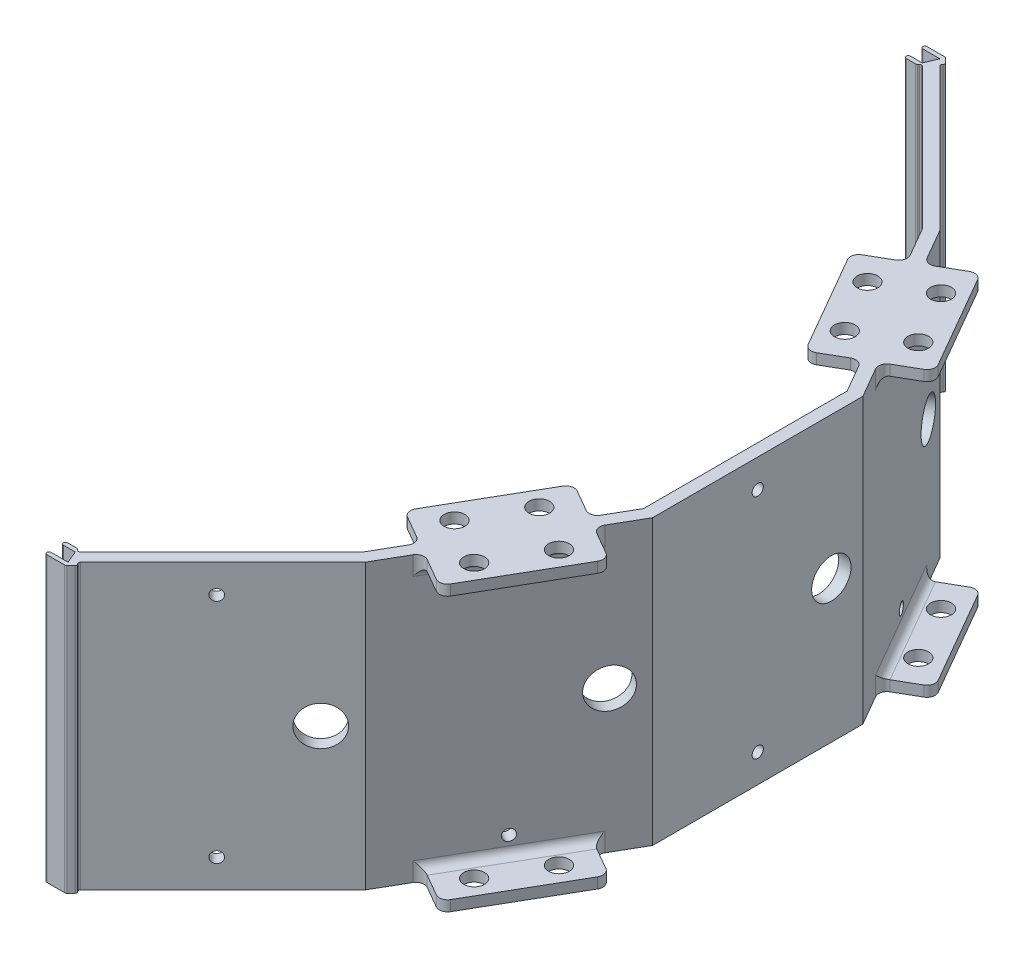
SolidWorks part; units mm, degrees
material "ABS"
ref_plane "Front Plane" through (0, 0, 0) normal (0, 0, 1) x (1, 0, 0)
ref_plane "Top Plane" through (0, 0, 0) normal (0, 1, 0) x (1, 0, 0)
ref_plane "Right Plane" through (0, 0, 0) normal (1, 0, 0) x (0, 0, -1)
sketch "Sketch1" plane through (0, 0, 0) normal (0, 1, 0) x (1, 0, 0)
  line L0 (-303.5027, 0) -> (303.5027, 0) construction
  line L1 (-223.52, -111.125) -> (223.52, -111.125)
  line L2 (-228.6, -106.045) -> (-228.6, 106.045)
  line L3 (-223.52, 111.125) -> (223.52, 111.125)
  line L4 (228.6, -106.045) -> (228.6, 106.045)
  line L5 (-228.6, -111.125) -> (228.6, 111.125) construction
  line L6 (-228.6, 111.125) -> (228.6, -111.125) construction
  line L7 (-303.5027, 36.5125) -> (303.5027, 36.5125) construction
  line L8 (-303.5027, -36.5125) -> (303.5027, -36.5125) construction
  line L9 (127, 111.125) -> (127, -111.125) construction
  line L10 (-142.24, 111.125) -> (-142.24, -111.125) construction
  arc A0 (223.52, 111.125) -> (228.6, 106.045) centre (223.52, 106.045) cw
  arc A1 (223.52, -111.125) -> (228.6, -106.045) centre (223.52, -106.045) ccw
  arc A2 (-223.52, -111.125) -> (-228.6, -106.045) centre (-223.52, -106.045) cw
  arc A3 (-228.6, 106.045) -> (-223.52, 111.125) centre (-223.52, 106.045) cw
  circle A4 centre (127, 36.5125) radius 2.54
  circle A5 centre (127, -36.5125) radius 2.54
  circle A6 centre (-142.24, 36.5125) radius 2.54
  circle A7 centre (-142.24, -36.5125) radius 2.54
  circle A8 centre (209.55, 0) radius 6.35
  point P0 (0, 0)
  point P20 (0, 0)
  point P37 (228.6, 0)
  dimension "D3" = 5.08
  dimension "D7" = 5.08
  dimension "D9" = 12.7
  dimension "D1" = 222.25
  dimension "D2" = 457.2
  dimension "D6" = 269.24
  dimension "D8" = 101.6
  dimension "D10" = 19.05
  dimension "D4" = 36.5125
  dimension "D5" = 36.5125
extrude "mainbaseplate" add sketch "Sketch1" along normal blind 3
sketch "Sketch2" plane through (0, 0, 0) normal (0, -1, 0) x (1, 0, 0)
  circle A0 centre (-142.24, 36.5125) radius 2.54 construction
  circle A1 centre (-142.24, -36.5125) radius 2.54 construction
  circle A2 centre (127, -36.5125) radius 2.54 construction
  circle A3 centre (127, 36.5125) radius 2.54 construction
  circle A4 centre (-142.24, 36.5125) radius 2.54
  circle A5 centre (-142.24, -36.5125) radius 2.54
  circle A6 centre (127, -36.5125) radius 2.54
  circle A7 centre (127, 36.5125) radius 2.54
  circle A8 centre (127, 36.5125) radius 6.096
  circle A9 centre (127, -36.5125) radius 6.096
  circle A10 centre (-142.24, -36.5125) radius 6.096
  circle A11 centre (-142.24, 36.5125) radius 6.096
  dimension "D1" = 12.192
extrude "BaseBoss-Extrude2" add sketch "Sketch2" along normal blind 10.16
sketch "Sketch3" plane through (0, 0, 0) normal (0, -1, 0) x (1, 0, 0)
  line L0 (-228.6, 0) -> (228.6, 0) construction
  line L1 (-228.6, -106.045) -> (-228.6, 106.045) construction
  line L2 (228.6, 106.045) -> (228.6, -106.045) construction
  line L3 (-228.6, 28.4) -> (-73.2, 28.4)
  line L4 (-228.6, -25.4) -> (-76.2, -25.4)
  line L6 (-228.6, 25.4) -> (-76.2, 25.4)
  line L7 (-76.2, -25.4) -> (-76.2, 25.4)
  line L8 (-228.6, -25.4) -> (-76.2, 25.4) construction
  line L9 (-228.6, 25.4) -> (-76.2, -25.4) construction
  line L10 (-73.2, -28.4) -> (-73.2, 28.4)
  line L11 (-228.6, -28.4) -> (-73.2, -28.4)
  line L12 (-228.6, 28.4) -> (-228.6, 25.4)
  line L13 (-228.6, -25.4) -> (-228.6, -28.4)
  point P6 (-152.4, 0)
  dimension "D1" = 50.8
  dimension "D2" = 152.4
  dimension "D3" = 76.2
  dimension "D4" = 3
extrude "Drive BatteryBoss-Extrude1" [suppressed] add sketch "Sketch3" along normal blind 28.575
sketch "Sketch4" [suppressed] plane through (0, -28.575, 0) normal (0, -1, 0) x (1, 0, 0)
  line L1 (-228.6, 28.4) -> (-73.2, 28.4)
  line L2 (-228.6, 28.4) -> (-228.6, -28.4)
  line L3 (-228.6, -28.4) -> (-73.2, -28.4)
  line L4 (-73.2, 28.4) -> (-73.2, -28.4)
extrude "drive Battery CapBoss-Extrude2" [suppressed] add sketch "Sketch4" along normal blind 3
sketch "Sketch5" [suppressed] plane through (0, -31.575, 0) normal (0, -1, 0) x (1, 0, 0)
  line L0 (-98.6, -28.4) -> (-73.2, -3)
  line L1 (-228.6, -28.4) -> (-73.2, -28.4) construction
  line L2 (-73.2, -28.4) -> (-73.2, 28.4) construction
  line L3 (-73.2, -3) -> (-52.1474, -3)
  line L4 (-52.1474, -3) -> (-52.1474, -43.6373)
  line L5 (-52.1474, -43.6373) -> (-98.6, -43.6373)
  line L6 (-98.6, -43.6373) -> (-98.6, -28.4)
  dimension "D1" = 25.4
  dimension "D2" = 25.4
  dimension "D3" = 21.0526
  dimension "D4" = 15.2373
extrude "Drive batterycutoutCut-Extrude1" [suppressed] cut sketch "Sketch5" against normal up to surface (31.575 mm away)
sketch "Sketch6" plane through (0, 3, 0) normal (0, 1, 0) x (1, 0, 0)
  line L0 (-228.6, 0) -> (228.6, 0) construction
  line L1 (-228.6, 106.045) -> (-228.6, -106.045) construction
  line L2 (228.6, -106.045) -> (228.6, 106.045) construction
  line L3 (-63.5, -41.1) -> (66.5, -41.1)
  line L4 (-63.5, -38.1) -> (63.5, -38.1)
  line L6 (-63.5, 38.1) -> (63.5, 38.1)
  line L7 (63.5, -38.1) -> (63.5, 38.1)
  line L8 (-63.5, -38.1) -> (63.5, 38.1) construction
  line L9 (-63.5, 38.1) -> (63.5, -38.1) construction
  line L10 (66.5, -41.1) -> (66.5, 41.1)
  line L11 (-63.5, 41.1) -> (66.5, 41.1)
  line L12 (-63.5, -41.1) -> (-63.5, -38.1)
  line L13 (-63.5, 38.1) -> (-63.5, 41.1)
  point P6 (0, 0)
  dimension "D1" = 127
  dimension "D2" = 76.2
  dimension "D4" = 63.5
  dimension "D3" = 3
extrude "PiBatteryBoxBoss-Extrude3" [suppressed] add sketch "Sketch6" along normal blind 25.4
sketch "Sketch7" [suppressed] plane through (0, 28.4, 0) normal (0, 1, 0) x (1, 0, 0)
  line L1 (66.5, 41.1) -> (-63.5, 41.1)
  line L2 (66.5, 41.1) -> (66.5, -41.1)
  line L3 (66.5, -41.1) -> (-63.5, -41.1)
  line L4 (-63.5, 41.1) -> (-63.5, -41.1)
extrude "PibatterytopBoss-Extrude4" [suppressed] add sketch "Sketch7" along normal blind 3
sketch "Sketch8" [suppressed] plane through (66.5, 0, 0) normal (1, 0, 0) x (0, 0, -1)
  line L0 (-38.1, 28.4) -> (38.1, 3) construction
  line L1 (38.1, 28.4) -> (-38.1, 28.4) construction
  line L2 (-31.75, 3) -> (31.75, 3)
  line L3 (-31.75, 3) -> (-31.75, 28.4)
  line L4 (-31.75, 28.4) -> (31.75, 28.4)
  line L5 (31.75, 3) -> (31.75, 28.4)
  line L6 (-31.75, 3) -> (31.75, 28.4) construction
  line L7 (-31.75, 28.4) -> (31.75, 3) construction
  point P2 (0, 15.7)
  dimension "D1" = 31.75
extrude "pibatterywiresCut-Extrude2" [suppressed] cut sketch "Sketch8" against normal blind 13.16
sketch "Sketch9" [suppressed] plane through (0, 31.4, 0) normal (0, 1, 0) x (1, 0, 0)
  line L0 (-63.5, 41.1) -> (66.5, -41.1) construction
  line L1 (-63.5, 0) -> (66.5, 0) construction
  line L2 (-5.08, -24.489) -> (52.92, -24.489) construction
  line L3 (-5.08, -24.489) -> (-5.08, 24.511) construction
  line L4 (-5.08, 24.511) -> (52.92, 24.511) construction
  line L5 (52.92, -24.489) -> (52.92, 24.511) construction
  line L6 (-5.08, -24.489) -> (52.92, 24.511) construction
  line L7 (-5.08, 24.511) -> (52.92, -24.489) construction
  line L8 (49.11, 20.701) -> (56.73, 20.701)
  line L9 (49.11, 20.701) -> (49.11, 28.321)
  line L10 (49.11, 28.321) -> (56.73, 28.321)
  line L11 (56.73, 20.701) -> (56.73, 28.321)
  line L12 (49.11, 20.701) -> (56.73, 28.321) construction
  line L13 (49.11, 28.321) -> (56.73, 20.701) construction
  line L14 (49.11, -28.299) -> (56.73, -28.299)
  line L16 (49.11, -20.679) -> (56.73, -20.679)
  line L18 (49.11, -28.299) -> (56.73, -20.679) construction
  line L19 (49.11, -20.679) -> (56.73, -28.299) construction
  line L20 (-8.89, 20.701) -> (-1.27, 20.701)
  line L21 (-8.89, 20.701) -> (-8.89, 28.321)
  line L22 (-8.89, 28.321) -> (-1.27, 28.321)
  line L23 (-1.27, 20.701) -> (-1.27, 28.321)
  line L24 (-8.89, 20.701) -> (-1.27, 28.321) construction
  line L25 (-8.89, 28.321) -> (-1.27, 20.701) construction
  line L26 (-8.89, -27.7078) -> (-1.27, -27.7078)
  line L27 (-8.89, -27.7078) -> (-8.89, -21.2702)
  line L28 (-8.89, -21.2702) -> (-1.27, -21.2702)
  line L29 (-1.27, -27.7078) -> (-1.27, -21.2702)
  line L30 (-8.89, -27.7078) -> (-1.27, -21.2702) construction
  line L31 (-8.89, -21.2702) -> (-1.27, -27.7078) construction
  line L32 (-63.5, 41.1) -> (-63.5, -41.1) construction
  line L33 (66.5, -41.1) -> (66.5, 41.1) construction
  line L34 (56.73, -20.679) -> (56.73, -28.299)
  line L35 (49.11, -20.679) -> (49.11, -28.299)
  circle A0 centre (52.92, 24.511) radius 1.35
  circle A1 centre (-5.08, 24.511) radius 1.35
  circle A2 centre (-5.08, -24.489) radius 1.35
  circle A3 centre (52.92, -24.489) radius 1.35
  point P4 (-8.057, 0)
  dimension "D3" = 2.7
  dimension "D4" = 7.62
  dimension "D1" = 58
  dimension "D2" = 49
  dimension "D5" = 7.62
  dimension "D6" = 7.62
  dimension "D7" = 7.62
  dimension "D8" = 7.62
  dimension "D9" = 7.62
  dimension "D10" = 58.42
  dimension "D11" = 24.511
  dimension "D12" = 7.62
extrude "PiBoardBoss-Extrude5" [suppressed] add sketch "Sketch9" along normal blind 3
sketch "Sketch10" plane through (0, 3, 0) normal (0, 1, 0) x (1, 0, 0)
  line L0 (228.6, 0) -> (-228.6, 0) construction
  line L1 (228.6, -106.045) -> (228.6, 106.045) construction
  line L2 (-228.6, 106.045) -> (-228.6, -106.045) construction
  line L3 (104.95, 18.875) -> (174.45, 18.875)
  line L4 (107.95, -15.875) -> (171.45, -15.875)
  line L5 (107.95, -15.875) -> (107.95, -6.175)
  line L6 (107.95, 15.875) -> (171.45, 15.875)
  line L7 (171.45, -15.875) -> (171.45, 15.875)
  line L8 (107.95, -15.875) -> (171.45, 15.875) construction
  line L9 (107.95, 15.875) -> (171.45, -15.875) construction
  line L10 (174.45, -18.875) -> (174.45, 18.875)
  line L11 (104.95, -18.875) -> (174.45, -18.875)
  line L12 (104.95, -18.875) -> (104.95, -6.175)
  line L13 (104.95, 6.175) -> (107.95, 6.175)
  line L14 (104.95, -6.175) -> (107.95, -6.175)
  line L15 (104.95, 6.175) -> (104.95, 18.875)
  line L16 (104.95, -18.875) -> (104.95, 18.875) construction
  line L17 (107.95, 6.175) -> (107.95, 15.875)
  line L18 (107.95, -15.875) -> (107.95, 15.875) construction
  point P6 (139.7, 0)
  dimension "D1" = 31.75
  dimension "D2" = 63.5
  dimension "D3" = 139.7
  dimension "D5" = 12.7
  dimension "D6" = 12.7
  dimension "D4" = 3
extrude "PanTilt-Extrude6" [suppressed] add sketch "Sketch10" along normal blind 53.34
sketch "Sketch11" [suppressed] plane through (0, 56.34, 0) normal (0, 1, 0) x (1, 0, 0)
  line L1 (104.95, 18.875) -> (174.45, 18.875)
  line L2 (104.95, 18.875) -> (104.95, -18.875)
  line L3 (104.95, -18.875) -> (174.45, -18.875)
  line L4 (174.45, 18.875) -> (174.45, -18.875)
extrude "Boss-Extrude7" [suppressed] add sketch "Sketch11" along normal blind 3
sketch "Sketch12" [suppressed] plane through (0, 59.34, 0) normal (0, 1, 0) x (1, 0, 0)
  line L0 (104.95, 0) -> (174.45, 0) construction
  line L1 (104.95, 18.875) -> (104.95, -18.875) construction
  line L2 (174.45, -18.875) -> (174.45, 18.875) construction
  line L3 (118.745, 1.9377) -> (104.95, 1.9377)
  line L4 (118.745, -10.795) -> (160.655, -10.795)
  line L5 (118.745, -10.795) -> (118.745, -1.9901)
  line L6 (118.745, 10.795) -> (160.655, 10.795)
  line L7 (160.655, -10.795) -> (160.655, 10.795)
  line L8 (118.745, -10.795) -> (160.655, 10.795) construction
  line L9 (118.745, 10.795) -> (160.655, -10.795) construction
  line L10 (115.57, -5.08) -> (163.83, -5.08) construction
  line L11 (115.57, -5.08) -> (115.57, 5.08) construction
  line L12 (115.57, 5.08) -> (163.83, 5.08) construction
  line L13 (163.83, -5.08) -> (163.83, 5.08) construction
  line L14 (115.57, -5.08) -> (163.83, 5.08) construction
  line L15 (115.57, 5.08) -> (163.83, -5.08) construction
  line L16 (118.745, -1.9901) -> (104.95, -1.9901)
  line L17 (118.745, 1.9377) -> (118.745, 10.795)
  line L18 (104.95, 1.9377) -> (95.8416, 0)
  line L19 (95.8416, 0) -> (104.95, -1.9901)
  circle A0 centre (163.83, 5.08) radius 2.0193
  circle A1 centre (163.83, -5.08) radius 2.0193
  circle A2 centre (115.57, 5.08) radius 2.0193
  circle A3 centre (115.57, -5.08) radius 2.0193
  point P6 (139.7, 0)
  point P11 (139.7, 0)
  dimension "D5" = 4.0386
  dimension "D1" = 21.59
  dimension "D2" = 41.91
  dimension "D3" = 48.26
  dimension "D4" = 10.16
  dimension "D6" = 1.9377
  dimension "D7" = 1.9901
extrude "Cut-Extrude3" [suppressed] cut sketch "Sketch12" against normal up to surface (56.34 mm away)
sketch "Sketch13" plane through (0, 3, 0) normal (0, 1, 0) x (1, 0, 0)
  line L0 (228.6, 0) -> (-228.6, 0) construction
  line L1 (228.6, -106.045) -> (228.6, 106.045) construction
  line L2 (-228.6, 106.045) -> (-228.6, -106.045) construction
  line L3 (198.12, 0) -> (198.12, 25.4)
  line L4 (198.12, 25.4) -> (172.72, 69.3941)
  line L5 (172.72, 69.3941) -> (136.799, 105.3151)
  line L6 (198.12, 25.4) -> (198.12, 129.9736) construction
  line L7 (172.72, 69.3941) -> (172.72, 97.5573) construction
  line L8 (136.799, 105.3151) -> (-185.781, 105.3151)
  line L9 (-185.781, 105.3151) -> (-221.702, 69.3941)
  line L10 (-221.702, 69.3941) -> (-221.702, 0)
  line L11 (-185.781, 105.3151) -> (-290.6809, 105.3151) construction
  line L12 (195.12, 0) -> (195.12, 24.5962)
  line L13 (195.12, 24.5962) -> (170.3194, 67.552)
  line L14 (170.3194, 67.552) -> (135.5563, 102.3151)
  line L15 (135.5563, 102.3151) -> (-184.5384, 102.3151)
  line L16 (-184.5384, 102.3151) -> (-218.702, 68.1514)
  line L17 (-218.702, 68.1514) -> (-218.702, 0)
  line L18 (172.72, -69.3941) -> (172.72, -97.5573) construction
  line L19 (198.12, -25.4) -> (198.12, -129.9736) construction
  line L20 (-218.702, -68.1514) -> (-218.702, 0)
  line L21 (-184.5384, -102.3151) -> (-218.702, -68.1514)
  line L22 (135.5563, -102.3151) -> (-184.5384, -102.3151)
  line L23 (170.3194, -67.552) -> (135.5563, -102.3151)
  line L24 (195.12, -24.5962) -> (170.3194, -67.552)
  line L25 (195.12, 0) -> (195.12, -24.5962)
  line L26 (-221.702, -69.3941) -> (-221.702, 0)
  line L27 (-185.781, -105.3151) -> (-221.702, -69.3941)
  line L28 (136.799, -105.3151) -> (-185.781, -105.3151)
  line L29 (172.72, -69.3941) -> (136.799, -105.3151)
  line L30 (198.12, -25.4) -> (172.72, -69.3941)
  line L31 (198.12, 0) -> (198.12, -25.4)
  line L32 (136.799, -105.3151) -> (135.5563, -102.3151)
  line L33 (135.5563, 102.3151) -> (136.799, 105.3151)
  line L34 (137.9705, 104.1435) -> (138.6777, 104.8506)
  line L35 (138.6777, 104.8506) -> (137.2132, 106.3151)
  line L36 (137.2132, 106.3151) -> (132.1937, 106.3151)
  line L37 (132.1937, 106.3151) -> (132.1937, 105.3151)
  line L38 (132.1937, 106.3151) -> (132.1937, -67.049) construction
  line L39 (135.8492, 102.0222) -> (135.1421, 101.3151)
  line L40 (135.1421, 101.3151) -> (135.1421, 101.3151)
  line L41 (135.1421, 101.3151) -> (132.1937, 101.3151)
  line L42 (132.1937, 101.3151) -> (132.1937, 102.3151)
  line L43 (132.1937, -67.049) -> (132.1937, -124.425) construction
  line L44 (135.8492, -102.0222) -> (135.1421, -101.3151)
  line L45 (135.1421, -101.3151) -> (135.1421, -101.3151)
  line L46 (135.1421, -101.3151) -> (132.1937, -101.3151)
  line L47 (132.1937, -101.3151) -> (132.1937, -102.3151)
  line L48 (132.1937, -106.3151) -> (132.1937, -105.3151)
  line L49 (137.2132, -106.3151) -> (132.1937, -106.3151)
  line L50 (138.6777, -104.8506) -> (137.2132, -106.3151)
  line L51 (137.9705, -104.1435) -> (138.6777, -104.8506)
  point P58 (0, 0)
  point P59 (0, 0)
  point P60 (0, 0)
  point P61 (0, 0)
  dimension "D1" = 30.48
  dimension "D2" = 25.4
  dimension "D3" = 30
  dimension "D4" = 50.8
  dimension "D5" = 45
  dimension "D6" = 50.8
  dimension "D7" = 322.58
  dimension "D8" = 50.8
  dimension "D9" = 45
  dimension "D11" = 1
  dimension "D12" = 1
  dimension "D13" = 1
  dimension "D15" = 1
  dimension "D10" = 3
extrude "Bottom Shell WallsBoss-Extrude8" add sketch "Sketch13" along normal blind 68.58 contours L33 L14 L13 L12 L25 L24 L23 L32 L29 L30 L31 L3 L4 L5 | L51 L29 L28 L48 L49 L50 | L46 L47 L22 L23 L44 L45 | L36 L37 L8 L5 L34 L35 | L42 L41 L40 L39 L14 L15 region at (195.9227, 3, 12.7) region at (135.4596, 3, -105.6407) region at (135.4596, 3, 105.6407) region at (133.881, 3, -101.8296) region at (133.881, 3, 101.8296)
sketch "Sketch14" plane through (121.057, 0, -121.057) normal (0.7071, 0, -0.7071) x (-0.7071, 0, -0.7071)
  line L0 (-47.6625, 71.58) -> (-47.6625, 3) construction
  line L1 (-73.0625, 71.58) -> (-22.2625, 71.58) construction
  line L2 (-73.0625, 3) -> (-23.9193, 3) construction
  line L3 (-47.6625, 37.29) -> (-25.0131, 37.29) construction
  circle A0 centre (-47.6625, 64.722) radius 1.3526
  circle A1 centre (-47.6625, 9.858) radius 1.3526
  circle A2 centre (-29.8825, 37.29) radius 4.7625
  point P10 (-47.6625, 37.29)
  dimension "D1" = 2.7051
  dimension "D4" = 9.525
  dimension "D2" = 54.864
  dimension "D3" = 27.432
  dimension "D5" = 17.78
extrude "Sharp1Cut-Extrude4" cut sketch "Sketch14" against normal blind 12.7
sketch "Sketch15" plane through (159.5885, 0, -92.1385) normal (0.866, 0, -0.5) x (-0.5, 0, -0.866)
  line L0 (-51.663, 71.58) -> (-51.663, 3) construction
  line L1 (-77.063, 71.58) -> (-26.263, 71.58) construction
  line L2 (-77.063, 3) -> (-26.263, 3) construction
  line L3 (-51.663, 37.29) -> (-29.7061, 37.29) construction
  circle A0 centre (-51.663, 64.722) radius 1.3526
  circle A1 centre (-51.663, 9.858) radius 1.3526
  circle A2 centre (-33.883, 37.29) radius 4.7625
  point P10 (-51.663, 37.29)
  dimension "D1" = 2.7051
  dimension "D4" = 9.525
  dimension "D2" = 27.432
  dimension "D3" = 54.864
  dimension "D5" = 17.78
extrude "Sharp2Cut-Extrude5" cut sketch "Sketch15" against normal blind 7.62
sketch "Sketch16" plane through (198.12, 0, 0) normal (1, 0, 0) x (0, 0, -1)
  line L0 (0, 71.58) -> (0, 3) construction
  line L1 (-25.4, 71.58) -> (25.4, 71.58) construction
  line L2 (-25.4, 3) -> (25.4, 3) construction
  line L3 (0, 37.29) -> (21.2381, 37.29) construction
  circle A0 centre (0, 64.722) radius 1.3526
  circle A1 centre (0, 9.858) radius 1.3525
  circle A2 centre (17.78, 37.29) radius 4.7625
  dimension "D1" = 2.7051
  dimension "D4" = 9.525
  dimension "D2" = 27.432
  dimension "D3" = 54.864
  dimension "D5" = 17.78
extrude "Sharp3Cut-Extrude6" cut sketch "Sketch16" against normal blind 7.62
sketch "Sketch17" plane through (159.5885, 0, 92.1385) normal (0.866, 0, 0.5) x (0.5, 0, -0.866)
  line L0 (51.663, 71.58) -> (51.663, 3) construction
  line L1 (26.263, 71.58) -> (77.063, 71.58) construction
  line L2 (26.263, 3) -> (77.063, 3) construction
  line L3 (51.663, 37.29) -> (70.4023, 37.29) construction
  circle A0 centre (51.663, 64.722) radius 1.3526
  circle A1 centre (51.663, 9.858) radius 1.3526
  circle A2 centre (69.443, 37.29) radius 4.7625
  dimension "D1" = 2.7051
  dimension "D2" = 2.7051
  dimension "D3" = 9.525
  dimension "D4" = 17.78
  dimension "D5" = 27.432
  dimension "D6" = 54.864
extrude "SharpCut-Extrude7" cut sketch "Sketch17" against normal blind 7.62
sketch "Sketch18" plane through (121.057, 0, 121.057) normal (0.7071, 0, 0.7071) x (0.7071, 0, -0.7071)
  line L0 (47.6625, 71.58) -> (47.6625, 3) construction
  line L1 (22.2625, 71.58) -> (73.0625, 71.58) construction
  line L2 (23.9193, 3) -> (73.0625, 3) construction
  line L3 (25.604, 37.29) -> (69.7209, 37.29) construction
  circle A0 centre (47.6625, 64.722) radius 1.3526
  circle A1 centre (47.6625, 9.858) radius 1.3526
  circle A2 centre (65.4425, 37.29) radius 4.7625
  point P13 (47.6625, 37.29)
  dimension "D1" = 9.525
  dimension "D3" = 2.7051
  dimension "D4" = 2.7051
  dimension "D2" = 17.78
  dimension "D5" = 27.432
  dimension "D6" = 54.864
extrude "SharpCut-Extrude8" cut sketch "Sketch18" against normal blind 7.62
sketch "Sketch19" [suppressed] plane through (0, 71.58, 0) normal (0, 1, 0) x (1, 0, 0)
  line L0 (-223.52, -111.125) -> (223.52, -111.125) construction
  line L1 (228.6, -106.045) -> (228.6, 106.045) construction
  line L2 (223.52, 111.125) -> (-223.52, 111.125) construction
  line L3 (104.95, -111.125) -> (223.52, -111.125)
  line L4 (228.6, -106.045) -> (228.6, 106.045)
  line L5 (223.52, 111.125) -> (104.95, 111.125)
  line L6 (104.95, 111.125) -> (104.95, -111.125)
  arc A0 (223.52, -111.125) -> (228.6, -106.045) centre (223.52, -106.045) ccw construction
  arc A1 (228.6, 106.045) -> (223.52, 111.125) centre (223.52, 106.045) ccw construction
  arc A2 (223.52, -111.125) -> (228.6, -106.045) centre (223.52, -106.045) ccw
  arc A3 (228.6, 106.045) -> (223.52, 111.125) centre (223.52, 106.045) ccw
sketch "Sketch21" [suppressed] plane through (0, 74.58, 0) normal (0, 1, 0) x (1, 0, 0)
  line L0 (104.95, -18.875) -> (174.45, -18.875) construction
  line L1 (174.45, -18.875) -> (174.45, 18.875) construction
  line L2 (174.45, 18.875) -> (104.95, 18.875) construction
  line L3 (104.95, -18.875) -> (164.29, -18.875)
  line L4 (174.45, -8.715) -> (174.45, 8.715)
  line L5 (164.29, 18.875) -> (104.95, 18.875)
  line L6 (104.95, 18.875) -> (84.8462, 2.2825)
  line L7 (84.8462, 2.2825) -> (104.95, -18.875)
  arc A0 (164.29, -18.875) -> (174.45, -8.715) centre (164.29, -8.715) ccw
  arc A1 (174.45, 8.715) -> (164.29, 18.875) centre (164.29, 8.715) ccw
  circle A2 centre (127, -36.5125) radius 6.096 construction
  circle A3 centre (127, 36.5125) radius 6.096 construction
  circle A4 centre (127, -36.5125) radius 6.096
  circle A5 centre (127, 36.5125) radius 6.096
  dimension "D1" = 10.16
extrude "topsensorplateCut-Extrude4" [suppressed] cut sketch "Sketch21" against normal blind 8.08
sketch "Sketch22" [suppressed] plane through (0, 0, 0) normal (0, -1, 0) x (1, 0, 0)
  line L0 (228.6, 0) -> (-228.6, 0) construction
  line L1 (228.6, 106.045) -> (228.6, -106.045) construction
  line L2 (-228.6, 28.4) -> (-228.6, -28.4) construction
  line L3 (220.98, 0) -> (220.98, 76.2)
  line L4 (220.98, 76.2) -> (193.675, 103.505)
  line L5 (193.675, 103.505) -> (-25.4, 103.505)
  line L6 (-223.52, 111.125) -> (223.52, 111.125) construction
  line L7 (217.98, 0) -> (217.98, 74.9574)
  line L8 (217.98, 74.9574) -> (192.4324, 100.505)
  line L9 (192.4324, 100.505) -> (-25.4, 100.505)
  line L10 (-25.4, 103.505) -> (-25.4, 100.505)
  line L11 (217.98, 0) -> (217.98, -74.9574)
  line L12 (220.98, 0) -> (220.98, -76.2)
  line L13 (-25.4, -103.505) -> (-25.4, -100.505)
  line L14 (192.4324, -100.505) -> (-25.4, -100.505)
  line L15 (217.98, -74.9574) -> (192.4324, -100.505)
  line L16 (193.675, -103.505) -> (-25.4, -103.505)
  line L17 (220.98, -76.2) -> (193.675, -103.505)
  line L18 (-220.98, 28.4) -> (-220.98, 76.2)
  line L19 (-73.2, 28.4) -> (-228.6, 28.4) construction
  line L20 (-220.98, 76.2) -> (-193.548, 103.505)
  line L21 (-193.548, 103.505) -> (-127, 103.505)
  line L22 (-228.6, 28.4) -> (-228.6, 106.045) construction
  line L23 (-217.98, 28.4) -> (-217.98, 74.9533)
  line L24 (-217.98, 74.9533) -> (-192.3094, 100.505)
  line L25 (-192.3094, 100.505) -> (-127, 100.505)
  line L26 (-127, 103.505) -> (-127, 100.505)
  line L27 (-220.98, 28.4) -> (-217.98, 28.4)
  line L28 (-127, -103.505) -> (-127, -100.505)
  line L29 (-192.3094, -100.505) -> (-127, -100.505)
  line L30 (-217.98, -74.9533) -> (-192.3094, -100.505)
  line L31 (-217.98, -28.4) -> (-217.98, -74.9533)
  line L32 (-193.548, -103.505) -> (-127, -103.505)
  line L33 (-220.98, -76.2) -> (-193.548, -103.505)
  line L34 (-220.98, -28.4) -> (-220.98, -76.2)
  line L35 (-220.98, -28.4) -> (-217.98, -28.4)
  dimension "D1" = 7.62
  dimension "D2" = 7.62
  dimension "D3" = 76.2
  dimension "D4" = 34.925
  dimension "D5" = 254
  dimension "D7" = 7.62
  dimension "D8" = 76.2
  dimension "D9" = 7.62
  dimension "D10" = 101.6
  dimension "D11" = 35.052
  dimension "D6" = 3
  dimension "D12" = 3
sketch "Sketch23" [suppressed] plane through (0, 0, -103.505) normal (0, 0, -1) x (-1, 0, 0)
  line L0 (25.4, 0) -> (-193.675, 0) construction
  line L2 (-223.1134, -81.0052) -> (22.7571, -81.0052) construction
  line L3 (22.7571, -81.0052) -> (254.0819, -81.0052) construction
  circle A1 centre (-127, -81.0052) radius 63.5
  circle A2 centre (152.4, -81.0052) radius 63.5
  dimension "D1" = 81.0052
  dimension "D4" = 127
  dimension "D2" = 22.7571
  dimension "D3" = 223.1134
  dimension "D5" = 127
  dimension "D6" = 279.4
extrude "TireCut-Extrude5" [suppressed] cut sketch "Sketch23" against normal blind 25.4
sketch "Sketch28" [suppressed] plane through (0, 0, 103.505) normal (0, 0, 1) x (1, 0, 0)
  line L0 (-205.194, -45.72) -> (-93.1399, -108.4782)
  line L1 (-93.1399, -108.4782) -> (179.794, -45.72)
  line L2 (74.206, -45.72) -> (-102.0458, -69.7467)
  line L3 (-102.0458, -69.7467) -> (-127, -22.8065)
  arc A0 (-192.3094, -31.6141) -> (-205.194, -45.72) centre (-152.4, -81.0052) ccw construction
  arc A1 (-127, -22.8065) -> (-192.3094, -31.6141) centre (-152.4, -81.0052) ccw construction
  arc A2 (179.794, -45.72) -> (74.206, -45.72) centre (127, -81.0052) ccw construction
  arc A3 (-192.3094, -31.6141) -> (-205.194, -45.72) centre (-152.4, -81.0052) ccw
  arc A4 (-127, -22.8065) -> (-192.3094, -31.6141) centre (-152.4, -81.0052) ccw
  arc A5 (179.794, -45.72) -> (74.206, -45.72) centre (127, -81.0052) ccw
extrude "TireCut-Extrude8" [suppressed] cut sketch "Sketch28" against normal blind 35.56
sketch "Sketch30" [suppressed] plane through (0, 74.58, 0) normal (0, 1, 0) x (1, 0, 0)
  line L0 (-147.32, 0) -> (-228.6, 0) construction
  line L1 (-147.32, -111.125) -> (-147.32, 111.125) construction
  line L2 (-228.6, 106.045) -> (-228.6, -106.045) construction
  circle A0 centre (-166.37, 0) radius 6.35
  dimension "D1" = 12.7
  dimension "D2" = 19.05
extrude "Cut-Extrude10" [suppressed] cut sketch "Sketch30" against normal blind 11.684
sketch "Sketch31" [suppressed] plane through (0, 0, 0) normal (1, 0, 0) x (0, 0, -1)
  line L0 (102.3151, 71.58) -> (102.3151, 3) construction
  line L1 (-102.3151, 71.58) -> (-76.9151, 71.58)
  line L2 (-102.3151, 71.58) -> (-102.3151, 68.58)
  line L3 (-102.3151, 68.58) -> (-76.9151, 68.58)
  line L4 (102.3151, 71.58) -> (102.3151, 68.58)
  line L5 (-76.9151, 71.58) -> (-76.9151, 68.58)
  line L6 (76.9151, 71.58) -> (76.9151, 68.58)
  line L7 (76.9151, 71.58) -> (102.3151, 71.58)
  line L8 (76.9151, 68.58) -> (102.3151, 68.58)
  dimension "D1" = 3
  dimension "D2" = 25.4
  dimension "D3" = 25.4
fillet "Fillet1" radius 0.5 18 edges at (138.6777, 37.29, 104.8506) (137.9705, 37.29, 104.1435) (138.6777, 37.29, -104.8506) (137.9705, 37.29, -104.1435) (132.1937, 37.29, 101.3151) (132.1937, 37.29, 102.3151) (135.1421, 37.29, 101.3151) (135.8492, 37.29, 102.0222) (132.1937, 37.29, 105.3151) (132.1937, 37.29, 106.3151) (137.2132, 37.29, 106.3151) (135.1421, 37.29, -101.3151) (135.8492, 37.29, -102.0222) (132.1937, 37.29, -102.3151) (132.1937, 37.29, -101.3151) (132.1937, 37.29, -106.3151) (132.1937, 37.29, -105.3151) (137.2132, 37.29, -106.3151)
sketch "Sketch32" plane through (0, -10.16, 0) normal (0, -1, 0) x (1, 0, 0)
  line L1 (254.5459, -134.1156) -> (-317.1071, -134.1156)
  line L2 (254.5459, -134.1156) -> (254.5459, 140.3717)
  line L3 (254.5459, 140.3717) -> (-317.1071, 140.3717)
  line L4 (-317.1071, -134.1156) -> (-317.1071, 140.3717)
extrude "Cut-Extrude11" cut sketch "Sketch32" against normal up to surface (13.16 mm away) up to face at (144.5082, 3, 0)
sketch "Sketch34" plane through (0, 3, 0) normal (0, -1, 0) x (1, 0, 0)
  line L0 (177.92, 60.3874) -> (186.5803, 65.3874)
  line L5 (198.12, 25.4) -> (172.72, 69.3941) construction
  line L6 (186.5803, 65.3874) -> (201.5803, 39.4067)
  line L7 (181.6617, 27.9067) -> (166.6617, 53.8874)
  line L8 (166.6617, 53.8874) -> (175.3219, 58.8874)
  line L9 (195.12, 24.5962) -> (170.3194, 67.552) construction
  line L10 (201.5803, 39.4067) -> (181.6617, 27.9067)
  line L11 (194.0803, 52.397) -> (174.1617, 40.897) construction
  line L12 (191.621, 33.6567) -> (183.9986, 46.8591) construction
  line L13 (182.2501, 62.8874) -> (189.7501, 49.897) construction
  line L14 (198.12, 0) -> (15.3913, 0) construction
  line L15 (198.12, -25.4) -> (198.12, 25.4) construction
  line L16 (201.5803, -39.4067) -> (181.6617, -27.9067)
  line L17 (186.5803, -65.3874) -> (201.5803, -39.4067)
  line L18 (177.92, -60.3874) -> (186.5803, -65.3874)
  line L19 (166.6617, -53.8874) -> (175.3219, -58.8874)
  line L20 (181.6617, -27.9067) -> (166.6617, -53.8874)
  circle A0 centre (186.0001, 56.3922) radius 2.5
  circle A1 centre (174.7418, 49.8922) radius 2.5
  circle A2 centre (193.5001, 43.4019) radius 2.5
  circle A3 centre (182.2418, 36.9019) radius 2.5
  circle A4 centre (174.7418, -49.8922) radius 2.5
  circle A5 centre (186.0001, -56.3922) radius 2.5
  circle A6 centre (193.5001, -43.4019) radius 2.5
  circle A7 centre (182.2418, -36.9019) radius 2.5
  point P16 (185.42, 47.397)
  point P18 (186.0001, 56.3922)
  line M6 (170.3194, 67.552) -> (195.12, 24.5962)
  line M8 (195.12, -24.5962) -> (170.3194, -67.552)
  line M27 (172.72, -69.3941) -> (198.12, -25.4)
  line M29 (198.12, 25.4) -> (172.72, 69.3941)
  dimension "D4" = 5
  dimension "D1" = 10
  dimension "D2" = 10
  dimension "D3" = 30
extrude "Boss-Extrude8" add sketch "Sketch34" against normal blind 2.54 contours L18 L17 L16 A6 A5 M27 | L16 L20 L19 A4 A7 M8 | L10 L8 L7 A3 A1 M6 | L10 L6 L0 A0 A2 M29 region at (178.4918, 3, 43.397) region at (189.7501, 3, 49.897) region at (189.7501, 3, -49.897) region at (178.4918, 3, -43.397)
sketch "Sketch36" plane through (0, 71.58, 0) normal (0, 1, 0) x (1, 0, 0)
  line L0 (177.92, -60.3874) -> (186.5803, -65.3874) construction
  line L1 (186.5803, -65.3874) -> (201.5803, -39.4067) construction
  line L2 (201.5803, -39.4067) -> (181.6617, -27.9067) construction
  line L3 (181.6617, -27.9067) -> (166.6617, -53.8874) construction
  line L4 (166.6617, -53.8874) -> (175.3219, -58.8874) construction
  line L5 (166.6617, 53.8874) -> (175.3219, 58.8874) construction
  line L6 (181.6617, 27.9067) -> (166.6617, 53.8874) construction
  line L7 (201.5803, 39.4067) -> (181.6617, 27.9067) construction
  line L8 (186.5803, 65.3874) -> (201.5803, 39.4067) construction
  line L9 (177.92, 60.3874) -> (186.5803, 65.3874) construction
  line L10 (177.92, -60.3874) -> (186.5803, -65.3874)
  line L11 (186.5803, -65.3874) -> (201.5803, -39.4067)
  line L16 (201.5803, -39.4067) -> (181.6617, -27.9067)
  line L17 (181.6617, -27.9067) -> (166.6617, -53.8874)
  line L18 (166.6617, -53.8874) -> (175.3219, -58.8874)
  line L19 (166.6617, 53.8874) -> (175.3219, 58.8874)
  line L20 (181.6617, 27.9067) -> (166.6617, 53.8874)
  line L21 (201.5803, 39.4067) -> (181.6617, 27.9067)
  line L22 (186.5803, 65.3874) -> (201.5803, 39.4067)
  line L23 (177.92, 60.3874) -> (186.5803, 65.3874)
  line L24 (175.3219, 58.8874) -> (177.92, 60.3874)
  line L25 (175.3219, -58.8874) -> (177.92, -60.3874)
  circle A1 centre (186.0001, -56.3922) radius 2.5
  circle A2 centre (186.0001, -56.3922) radius 2.5
  circle A3 centre (182.2418, -36.9019) radius 2.5
  circle A4 centre (182.2418, -36.9019) radius 2.5
  circle A5 centre (193.5001, -43.4019) radius 2.5
  circle A6 centre (193.5001, -43.4019) radius 2.5
  circle A7 centre (174.7418, -49.8922) radius 2.5
  circle A8 centre (174.7418, -49.8922) radius 2.5
  circle A9 centre (182.2418, 36.9019) radius 2.5
  circle A10 centre (182.2418, 36.9019) radius 2.5
  circle A11 centre (193.5001, 43.4019) radius 2.5
  circle A12 centre (193.5001, 43.4019) radius 2.5
  circle A13 centre (186.0001, 56.3922) radius 2.5
  circle A14 centre (186.0001, 56.3922) radius 2.5
  circle A15 centre (174.7418, 49.8922) radius 2.5
  circle A16 centre (174.7418, 49.8922) radius 2.5
  line M23 (172.72, -69.3941) -> (198.12, -25.4)
  line M25 (198.12, 25.4) -> (172.72, 69.3941)
  line M44 (170.3194, 67.552) -> (195.12, 24.5962)
  line M46 (195.12, -24.5962) -> (170.3194, -67.552)
  dimension "D1" = 0
  dimension "D2" = 0
  dimension "D3" = 0
  dimension "D4" = 0
  dimension "D5" = 0
  dimension "D6" = 0
  dimension "D7" = 0
  dimension "D8" = 0
extrude "Boss-Extrude9" add sketch "Sketch36" against normal blind 2.54 contours L23 L21 L22 A14 A12 M25 | L21 L19 L20 A16 A10 M44 | L17 L18 L16 A8 A4 M46 | L11 L16 L10 A6 A2 M23 | L25 L16 M46 M23 | L24 L21 M44 M25 region at (189.7501, 71.58, 49.897) region at (184.121, 71.58, 46.647) region at (178.4918, 71.58, 43.397) region at (178.4918, 71.58, -43.397) region at (184.121, 71.58, -46.647) region at (189.7501, 71.58, -49.897)
fillet "Fillet2" radius 2 20 edges at (166.6617, 4.27, 53.8874) (181.6617, 4.27, 27.9067) (190.3219, 4.27, 32.9067) (175.3219, 4.27, 58.8874) (182.8219, 5.54, 45.897) (166.6617, 4.27, -53.8874) (181.6617, 4.27, -27.9067) (190.3219, 4.27, -32.9067) (175.3219, 4.27, -58.8874) (182.8219, 5.54, -45.897) (201.5803, 4.27, 39.4067) (186.5803, 4.27, 65.3874) (177.92, 4.27, 60.3874) (192.92, 4.27, 34.4067) (185.42, 5.54, 47.397) (201.5803, 4.27, -39.4067) (186.5803, 4.27, -65.3874) (177.92, 4.27, -60.3874) (192.92, 4.27, -34.4067) (185.42, 5.54, -47.397)
fillet "Fillet3" radius 2 20 edges at (181.6617, 70.31, 27.9067) (190.3219, 70.31, 32.9067) (175.3219, 70.31, 58.8874) (166.6617, 70.31, 53.8874) (182.8219, 69.04, 45.897) (190.3219, 70.31, -32.9067) (181.6617, 70.31, -27.9067) (166.6617, 70.31, -53.8874) (182.8219, 69.04, -45.897) (175.3219, 70.31, -58.8874) (192.92, 70.31, 34.4067) (201.5803, 70.31, 39.4067) (177.92, 70.31, 60.3874) (185.42, 69.04, 47.397) (186.5803, 70.31, 65.3874) (201.5803, 70.31, -39.4067) (186.5803, 70.31, -65.3874) (177.92, 70.31, -60.3874) (185.42, 69.04, -47.397) (192.92, 70.31, -34.4067)
